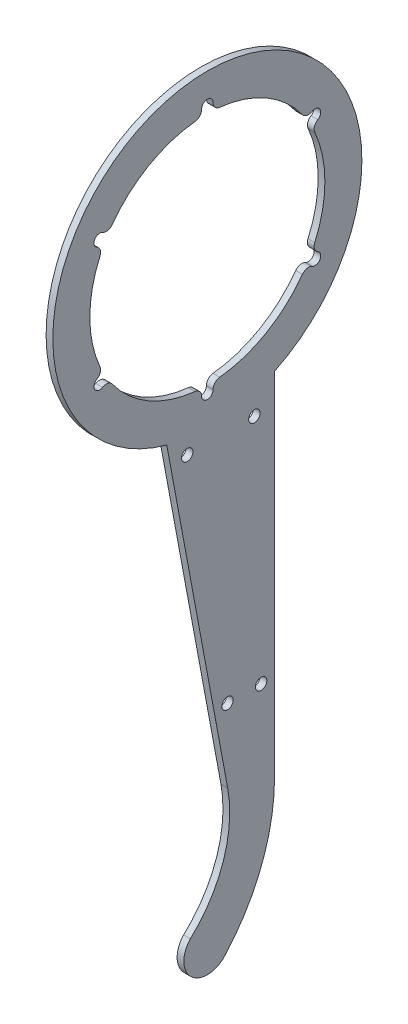
SolidWorks part; units mm, degrees
ref_plane "前视基准面" through (0, 0, 0) normal (0, 0, 1) x (1, 0, 0)
ref_plane "上视基准面" through (0, 0, 0) normal (0, 1, 0) x (1, 0, 0)
ref_plane "右视基准面" through (0, 0, 0) normal (1, 0, 0) x (0, 0, -1)
sketch "草图1" plane through (0, 0, 0) normal (1, 0, 0) x (0, 0, -1)
  line L10 (-12.0867, -44.3837) -> (6.0415, -141.8339)
  line L13 (20, -146.0922) -> (20, -41.4246)
  arc A21 (20, -41.4246) -> (-12.0867, -44.3837) centre (0, 0) ccw
  arc A22 (20, -146.0922) -> (5.2059, -184.6796) centre (-37.7208, -146.0922) cw
  arc A23 (5.2059, -184.6796) -> (-5.0762, -175.1801) centre (0, -180) cw
  arc A24 (-5.0762, -175.1801) -> (6.0415, -141.8339) centre (-29.6255, -148.4689) ccw construction
  arc A25 (6.0415, -141.8339) -> (-5.0762, -175.1801) centre (-29.6255, -148.4689) cw
  circle A26 centre (-6, -50) radius 1.7
  circle A27 centre (14, -50) radius 1.7
  circle A28 centre (6, -120) radius 1.7
  circle A29 centre (16, -120) radius 1.7
  arc A30 (1.7, -37) -> (3.6883, -34.7898) centre (3.9226, -37) cw
  arc A33 (1.7, -37) -> (-1.7, -37) centre (0, -37) cw
  arc A34 (-1.7, -37) -> (-3.6883, -34.7898) centre (-3.9226, -37) ccw
  arc A35 (-32.8929, -17.0278) -> (-31.973, -14.2008) centre (-34.0042, -15.1029) ccw
  arc A36 (-31.1929, -19.9722) -> (-32.8929, -17.0278) centre (-32.0429, -18.5) cw
  arc A37 (-31.1929, -19.9722) -> (-28.2847, -20.589) centre (-30.0817, -21.8971) cw
  arc A38 (-31.1929, 19.9722) -> (-28.2847, 20.589) centre (-30.0817, 21.8971) ccw
  arc A39 (-32.8929, 17.0278) -> (-31.1929, 19.9722) centre (-32.0429, 18.5) cw
  arc A40 (-32.8929, 17.0278) -> (-31.973, 14.2008) centre (-34.0042, 15.1029) cw
  arc A41 (1.7, 37) -> (3.6883, 34.7898) centre (3.9226, 37) ccw
  arc A42 (-1.7, 37) -> (1.7, 37) centre (0, 37) cw
  arc A43 (-1.7, 37) -> (-3.6883, 34.7898) centre (-3.9226, 37) cw
  arc A44 (32.8929, 17.0278) -> (31.973, 14.2008) centre (34.0042, 15.1029) ccw
  arc A45 (31.1929, 19.9722) -> (32.8929, 17.0278) centre (32.0429, 18.5) cw
  arc A46 (31.1929, 19.9722) -> (28.2847, 20.589) centre (30.0817, 21.8971) cw
  arc A47 (31.1929, -19.9722) -> (28.2847, -20.589) centre (30.0817, -21.8971) ccw
  arc A48 (32.8929, -17.0278) -> (31.1929, -19.9722) centre (32.0429, -18.5) cw
  arc A49 (32.8929, -17.0278) -> (31.973, -14.2008) centre (34.0042, -15.1029) cw
  arc A50 (-31.973, 14.2008) -> (-31.973, -14.2008) centre (0, 0) ccw
  arc A51 (-28.2847, -20.589) -> (-3.6883, -34.7898) centre (0, 0) ccw
  arc A52 (28.2847, -20.589) -> (3.6883, -34.7898) centre (0, 0) cw
  arc A53 (31.973, 14.2008) -> (31.973, -14.2008) centre (0, 0) cw
  arc A54 (28.2847, 20.589) -> (3.6883, 34.7898) centre (0, 0) ccw
  arc A55 (-3.6883, 34.7898) -> (-28.2847, 20.589) centre (0, 0) ccw
  point P79 (0, 0)
  dimension "D1" = 6
extrude "凸台-拉伸3" add sketch "草图1" along normal blind 2
